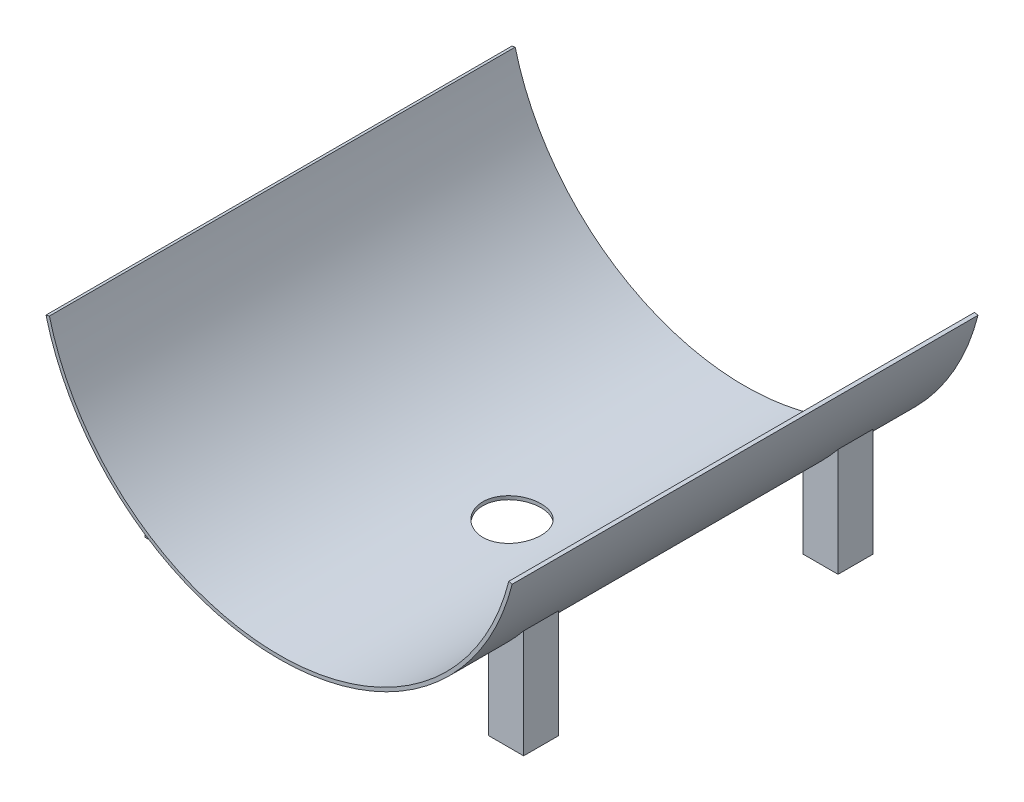
SolidWorks part; units mm, degrees
ref_plane "Front Plane" through (0, 0, 0) normal (0, 0, 1) x (1, 0, 0)
ref_plane "Top Plane" through (0, 0, 0) normal (0, 1, 0) x (1, 0, 0)
ref_plane "Right Plane" through (0, 0, 0) normal (1, 0, 0) x (0, 0, -1)
sketch "Sketch1" plane through (0, 0, 0) normal (0, 0, 1) x (1, 0, 0)
  line L1 (-241.8639, 173.5) -> (305.9882, 173.5) construction
  arc A0 (-197.2619, 173.5) -> (197.2619, 173.5) centre (0, 223.5) ccw
  dimension "D1" = 407
  dimension "D2" = 223.5
  dimension "D3" = 50
extrude "Extrude-Thin1" add sketch "Sketch1" along normal blind 400 thin thin type one direction wall 3
sketch "Sketch2" plane through (0, 0, 0) normal (0, 1, 0) x (1, 0, 0)
  line L5 (-165, -320) -> (-135, -320)
  line L6 (-165, -320) -> (-165, -350)
  line L11 (-165, -350) -> (-135, -350)
  line L12 (-135, -320) -> (-135, -350)
  line L17 (130, -320) -> (160, -320)
  line L18 (130, -320) -> (130, -350)
  line L23 (130, -350) -> (160, -350)
  line L24 (160, -320) -> (160, -350)
  line L25 (-165, -50) -> (-135, -50)
  line L26 (-165, -50) -> (-165, -80)
  line L27 (-165, -80) -> (-135, -80)
  line L28 (-135, -50) -> (-135, -80)
  line L29 (130, -50) -> (160, -50)
  line L30 (130, -50) -> (130, -80)
  line L31 (130, -80) -> (160, -80)
  line L32 (160, -50) -> (160, -80)
  line L34 (0, -400) -> (0, 0) construction
  line L36 (200.1699, 0) -> (-200.1699, 0) construction
  dimension "D1" = 30
  dimension "D2" = 265
  dimension "D3" = 135
  dimension "D4" = 240
  dimension "D5" = 50
extrude "Boss-Extrude1" add sketch "Sketch2" along normal up to surface (67.2398 mm away) up to face at (0, 94.8814, 200)
sketch "Sketch3" plane through (0, 0, 0) normal (0, 1, 0) x (1, 0, 0)
  line L0 (-197.2619, -400) -> (197.2619, -400) construction
  line L2 (0, -400) -> (0, 0) construction
  circle A0 centre (0, -200) radius 25
  point P4 (0, 0)
  dimension "D1" = 50
  dimension "D2" = 200
extrude "Cut-Extrude1" cut sketch "Sketch3" along normal through all
